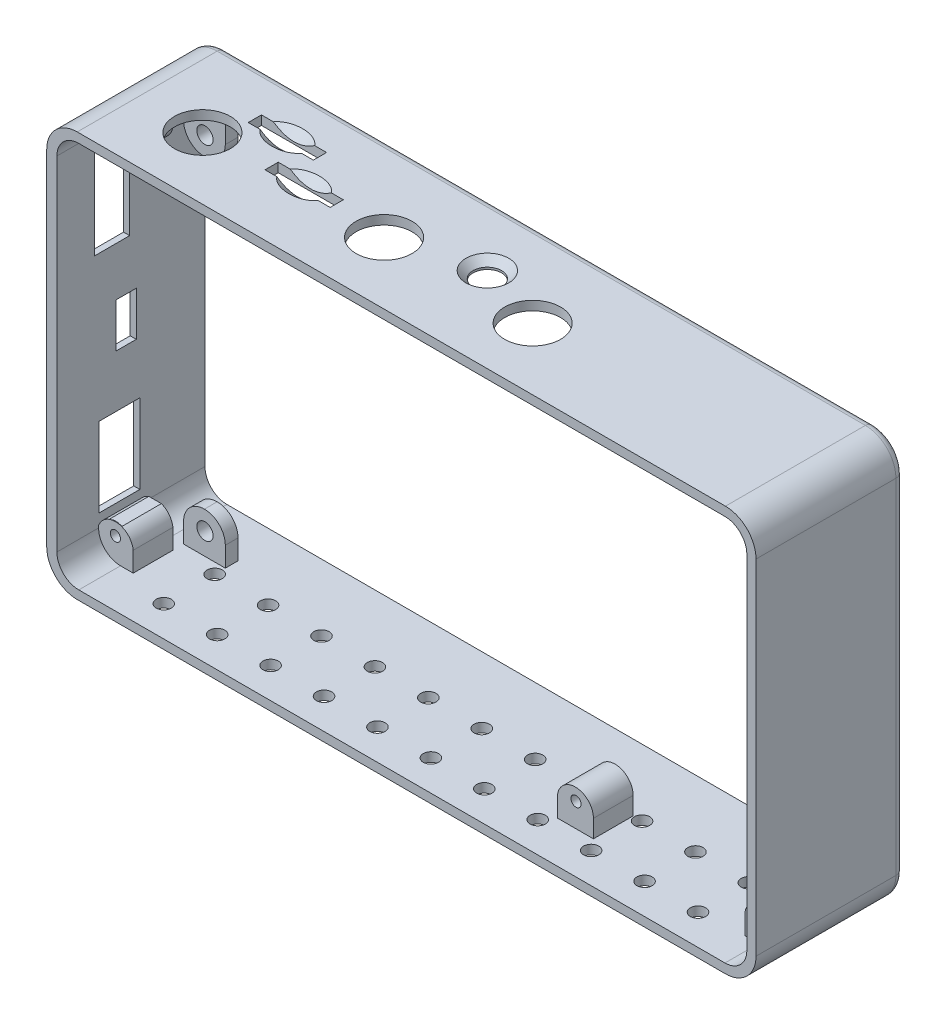
SolidWorks part; units mm, degrees
ref_plane "Спереди" through (0, 0, 0) normal (0, 0, 1) x (1, 0, 0)
ref_plane "Сверху" through (0, 0, 0) normal (0, 1, 0) x (1, 0, 0)
ref_plane "Справа" through (0, 0, 0) normal (1, 0, 0) x (0, 0, -1)
sketch "Эскиз1" plane through (0, 0, 0) normal (0, 0, 1) x (1, 0, 0)
  line L0 (-67.7, 32.8) -> (-67.7, -32.8)
  line L1 (-69.7, -33.9) -> (-69.7, 33.9)
  line L2 (-63.9, 38) -> (63.9, 38)
  line L3 (-64, 39.8) -> (64, 39.8)
  line L4 (-60.9, 34.5) -> (-60.9, 38)
  line L5 (-62.5165, 31.55) -> (-66.2835, 31.55)
  line L6 (-60.7, 33.8) -> (-60.7, 34.2)
  line L7 (29.55, 34.5) -> (29.55, 38)
  line L8 (22.45, 34.5) -> (22.45, 38)
  line L9 (56.9, 30) -> (56.5, 30)
  line L10 (60.7, 33.8) -> (60.7, 34.2)
  line L11 (60.9, 38) -> (60.9, 34.5)
  line L12 (67.9, -32.8) -> (67.9, 32.8)
  line L13 (69.7, 33.9) -> (69.7, -33.9)
  line L14 (60.9, -38) -> (60.9, -34.5)
  line L15 (67.9, -33) -> (67.9, -34)
  line L16 (59, -39.8) -> (62, -39.8)
  line L17 (59, -39.8) -> (-59, -39.8)
  line L18 (64, -39.8) -> (62, -39.8)
  line L19 (-63.9, -38) -> (63.9, -38)
  line L20 (22.45, -34.5) -> (22.45, -38)
  line L21 (29.55, -34.5) -> (29.55, -38)
  line L22 (-52.7, -33.8) -> (-52.7, -34.2)
  line L23 (-60.7, -33.8) -> (-60.7, -34.2)
  line L24 (-62, -39.8) -> (-64, -39.8)
  line L25 (-62, -39.8) -> (-59, -39.8)
  line L26 (-60.9, -34.5) -> (-60.9, -38)
  line L27 (-62.5165, -31.55) -> (-66.2835, -31.55)
  arc A0 (-63.9, 38) -> (-67.9, 34) centre (-63.9, 34) ccw
  circle A1 centre (-64.4, 34.5) radius 1
  arc A2 (-64, 39.8) -> (-69.7, 34.1) centre (-64, 34.1) ccw
  arc A3 (-62.5165, 31.55) -> (-60.9, 34.5) centre (-64.4, 34.5) ccw
  arc A4 (-66.2835, 31.55) -> (-62.5165, 31.55) centre (-64.4, 34.5) ccw
  arc A5 (-67.5623, 33) -> (-66.2835, 31.55) centre (-64.4, 34.5) ccw
  arc A6 (-60.7, 34.2) -> (-60.9, 35.4166) centre (-64.5, 34.2) ccw
  arc A7 (-60.7, 33.8) -> (-56.9, 30) centre (-56.9, 33.8) ccw
  arc A8 (-56.5, 30) -> (-52.7, 33.8) centre (-56.5, 33.8) ccw
  arc A9 (-48.9, 38) -> (-52.7, 34.2) centre (-48.9, 34.2) ccw
  circle A10 centre (-56.7, 33.7) radius 1.6
  arc A11 (22.45, 34.5) -> (29.55, 34.5) centre (26, 34.5) ccw
  circle A12 centre (26.1275, 34.6188) radius 1.5
  arc A13 (56.9, 30) -> (60.7, 33.8) centre (56.9, 33.8) ccw
  circle A14 centre (56.7, 33.7) radius 1.6
  arc A15 (52.7, 33.8) -> (56.5, 30) centre (56.5, 33.8) ccw
  arc A16 (52.7, 34.2) -> (48.9, 38) centre (48.9, 34.2) ccw
  arc A17 (60.9, 35.4166) -> (60.7, 34.2) centre (64.5, 34.2) ccw
  arc A18 (60.9, 34.5) -> (67.5623, 33) centre (64.4, 34.5) ccw
  circle A19 centre (64.4, 34.5) radius 1
  arc A20 (69.7, 34.1) -> (64, 39.8) centre (64, 34.1) ccw
  arc A21 (67.9, 34) -> (63.9, 38) centre (63.9, 34) ccw
  arc A22 (48.9, -38) -> (52.7, -34.2) centre (48.9, -34.2) ccw
  arc A23 (56.5, -30) -> (52.7, -33.8) centre (56.5, -33.8) ccw
  arc A24 (60.7, -33.8) -> (56.9, -30) centre (56.9, -33.8) ccw
  circle A25 centre (56.7, -33.7) radius 1.6
  arc A26 (67.5623, -33) -> (60.9, -34.5) centre (64.4, -34.5) ccw
  arc A27 (63.9, -38) -> (67.9, -34) centre (63.9, -34) ccw
  arc A28 (64, -39.8) -> (69.7, -34.1) centre (64, -34.1) ccw
  circle A29 centre (64.4, -34.5) radius 1
  circle A30 centre (26.1275, -33.3262) radius 1.5
  arc A31 (29.55, -34.5) -> (22.45, -34.5) centre (26, -34.5) ccw
  arc A32 (-52.7, -33.8) -> (-56.5, -30) centre (-56.5, -33.8) ccw
  arc A33 (-52.7, -34.2) -> (-48.9, -38) centre (-48.9, -34.2) ccw
  arc A34 (-56.9, -30) -> (-60.7, -33.8) centre (-56.9, -33.8) ccw
  circle A35 centre (-56.7, -33.7) radius 1.6
  arc A36 (-60.9, -35.4166) -> (-60.7, -34.2) centre (-64.5, -34.2) ccw
  arc A37 (-67.9, -34) -> (-63.9, -38) centre (-63.9, -34) ccw
  arc A38 (-69.7, -34.1) -> (-64, -39.8) centre (-64, -34.1) ccw
  arc A39 (-60.9, -34.5) -> (-62.5165, -31.55) centre (-64.4, -34.5) ccw
  arc A40 (-66.2835, -31.55) -> (-67.5623, -33) centre (-64.4, -34.5) ccw
  arc A41 (-62.5165, -31.55) -> (-66.2835, -31.55) centre (-64.4, -34.5) ccw
  circle A42 centre (-64.4, -33.4) radius 1
sketch "Эскиз2" plane through (0, 0, 0) normal (0, 0, 1) x (1, 0, 0)
  line L0 (-69.7, -33.9) -> (-69.7, 33.9) construction
  line L1 (-69.7, -39.8) -> (-69.7, 39.8)
  line L2 (-67.7, 32.8) -> (-67.7, -32.8) construction
  line L3 (-67.7, 38) -> (-67.7, -38)
  line L4 (-64, 39.8) -> (64, 39.8) construction
  line L5 (-69.7, 39.8) -> (69.7, 39.8)
  line L6 (-63.9, 38) -> (63.9, 38) construction
  line L7 (-67.7, 38) -> (67.9, 38)
  line L9 (69.7, 33.9) -> (69.7, -33.9) construction
  line L10 (69.7, 39.8) -> (69.7, -39.8)
  line L11 (67.9, -32.8) -> (67.9, 32.8) construction
  line L12 (67.9, -38) -> (67.9, 38)
  line L19 (-63.9, -38) -> (63.9, -38) construction
  line L20 (-67.7, -38) -> (67.9, -38)
  line L25 (59, -39.8) -> (-59, -39.8) construction
  line L26 (69.7, -39.8) -> (-69.7, -39.8)
  point P1 (-67.7, 37.7102)
  point P2 (69.7, 39.8)
  point P4 (-69.726, 39.8)
  point P5 (-69.7, 39.6686)
  point P8 (67.9, 38)
  point P9 (67.9, -38)
  point P12 (-67.7, 38)
  point P13 (67.7289, 38)
  point P15 (69.5498, 39.8)
  point P21 (67.7269, -38)
  point P22 (69.7, -39.8)
  point P24 (69.8908, -39.8)
  point P27 (-69.7, -39.8)
  point P28 (-67.7, -38)
  point P30 (-67.8826, -38)
  point P34 (-69.7, -39.5625)
  point P38 (0, 0)
  point P41 (0, 0)
  point P42 (0, 0)
  point P43 (0, 0)
  point P44 (-67.7, 37.9527)
other "Перо1"
extrude "Бобышка-Вытянуть1" add sketch "Эскиз2" along normal blind 29.1
fillet "Скругление2" radius 4.3 4 edges at (-67.7, 38, 14.55) (67.9, 38, 14.55) (67.9, -38, 14.55) (-67.7, -38, 14.55)
fillet "Скругление3" radius 6 4 edges at (-69.7, 39.8, 14.55) (69.7, 39.8, 14.55) (69.7, -39.8, 14.55) (-69.7, -39.8, 14.55)
fillet "Скругление4" radius 1.6 8 edges at (67.9426, 38.0426, 0) (69.7, 0, 0) (67.9426, -38.0426, 0) (0, -39.8, 0) (-67.9426, -38.0426, 0) (-69.7, 0, 0) (-67.9426, 38.0426, 0) (0, 39.8, 0)
sketch "Эскиз4" plane through (0, 0, 0) normal (0, 0, -1) x (-1, 0, 0)
  line L1 (-60.9, 38) -> (-52.7, 38)
  line L2 (-60.9, 38) -> (-60.9, 30)
  line L3 (-60.9, 30) -> (-52.7, 30)
  line L4 (-52.7, 38) -> (-52.7, 30)
  line L5 (60.9, 38) -> (52.7, 38)
  line L6 (60.9, 38) -> (60.9, 30)
  line L7 (60.9, 30) -> (52.7, 30)
  line L8 (52.7, 38) -> (52.7, 30)
  line L9 (60.9, -38) -> (52.7, -38)
  line L10 (60.9, -38) -> (60.9, -30)
  line L11 (60.9, -30) -> (52.7, -30)
  line L12 (52.7, -38) -> (52.7, -30)
  line L13 (-60.9, -38) -> (-52.7, -38)
  line L14 (-60.9, -38) -> (-60.9, -30)
  line L15 (-60.9, -30) -> (-52.7, -30)
  line L16 (-52.7, -38) -> (-52.7, -30)
extrude "Бобышка-Вытянуть2" add sketch "Эскиз4" against normal blind 11
sketch "Эскиз7" plane through (-52.7, 0, 0) normal (1, 0, 0) x (0, 0, -1)
  line L0 (-11, -38) -> (0, -38) construction
  line L1 (0, -30) -> (-8.5, -30)
  line L2 (0, -30) -> (0, -38)
  line L3 (0, -38) -> (-8.5, -38)
  line L4 (-8.5, -30) -> (-8.5, -38)
  dimension "D1" = 8.5
extrude "Вырез-Вытянуть1" cut sketch "Эскиз7" against normal blind 8.2
sketch "Эскиз8" plane through (-52.7, 0, 0) normal (1, 0, 0) x (0, 0, -1)
  line L0 (-11, 38) -> (0, 38) construction
  line L1 (0, 30) -> (-8.5, 30)
  line L2 (0, 30) -> (0, 38)
  line L3 (0, 38) -> (-8.5, 38)
  line L4 (-8.5, 30) -> (-8.5, 38)
  dimension "D1" = 8.5
extrude "Вырез-Вытянуть2" cut sketch "Эскиз8" against normal blind 8.2
sketch "Эскиз9" plane through (52.7, 0, 0) normal (-1, 0, 0) x (0, 0, 1)
  line L0 (11, 38) -> (0, 38) construction
  line L1 (0, 30) -> (8.5, 30)
  line L2 (0, 30) -> (0, 38)
  line L3 (0, 38) -> (8.5, 38)
  line L4 (8.5, 30) -> (8.5, 38)
  dimension "D1" = 8.5
extrude "Вырез-Вытянуть3" cut sketch "Эскиз9" against normal blind 8.2
sketch "Эскиз10" plane through (52.7, 0, 0) normal (-1, 0, 0) x (0, 0, 1)
  line L0 (11, -38) -> (0, -38) construction
  line L1 (0, -30) -> (8.5, -30)
  line L2 (0, -30) -> (0, -38)
  line L3 (0, -38) -> (8.5, -38)
  line L4 (8.5, -30) -> (8.5, -38)
  dimension "D1" = 8.5
extrude "Вырез-Вытянуть4" cut sketch "Эскиз10" against normal blind 8.2
sketch "Эскиз11" plane through (0, 0, 11) normal (0, 0, 1) x (1, 0, 0)
  circle A0 centre (-56.7, 33.7) radius 1.6 construction
  circle A1 centre (-56.7, 33.7) radius 1.6
  circle A2 centre (56.7, 33.7) radius 1.6 construction
  circle A3 centre (56.7, 33.7) radius 1.6
  circle A4 centre (56.7, -33.7) radius 1.6 construction
  circle A5 centre (56.7, -33.7) radius 1.6
  circle A6 centre (-56.7, -33.7) radius 1.6 construction
  circle A7 centre (-56.7, -33.7) radius 1.6
extrude "Вырез-Вытянуть5" cut sketch "Эскиз11" against normal blind 3
fillet "Скругление5" radius 4.1 8 edges at (60.9, -30, 9.75) (52.7, -30, 9.75) (52.7, 30, 9.75) (60.9, 30, 9.75) (-52.7, 30, 9.75) (-60.9, 30, 9.75) (-60.9, -30, 9.75) (-52.7, -30, 9.75)
sketch "Эскиз12" plane through (0, 0, 29.1) normal (0, 0, 1) x (1, 0, 0)
  line L0 (67.9, -33.7) -> (67.9, 33.7) construction
  line L1 (-67.7, 33.7) -> (-67.7, -33.7) construction
  line L2 (60.9, -38) -> (60.9, -34.5) construction
  line L3 (60.9, -38) -> (60.9, -34.5)
  line L4 (-63.4, -38) -> (63.6, -38) construction
  line L5 (-63.4, -38) -> (63.6, -38)
  line L6 (29.55, -34.5) -> (29.55, -38) construction
  line L7 (29.55, -34.5) -> (29.55, -38)
  line L8 (22.45, -34.5) -> (22.45, -38) construction
  line L9 (22.45, -34.5) -> (22.45, -38)
  line L10 (-60.9, -34.5) -> (-60.9, -38) construction
  line L11 (-60.9, -34.5) -> (-60.9, -38)
  line L12 (-67.7, 33.7) -> (-67.7, -33.7)
  line L13 (67.9, -33.7) -> (67.9, 33.7)
  line L14 (60.9, 38) -> (60.9, 34.5) construction
  line L15 (60.9, 38) -> (60.9, 34.5)
  line L16 (63.6, 38) -> (-63.4, 38) construction
  line L17 (63.6, 38) -> (-63.4, 38)
  line L18 (29.55, 34.5) -> (29.55, 38) construction
  line L19 (29.55, 34.5) -> (29.55, 38)
  line L20 (22.45, 34.5) -> (22.45, 38) construction
  line L21 (22.45, 34.5) -> (22.45, 38)
  line L22 (-60.9, 34.5) -> (-60.9, 38) construction
  line L23 (-60.9, 34.5) -> (-60.9, 38)
  line L24 (-60.9, -34.1) -> (-60.9, -34.5)
  arc A0 (60.9, 35.4166) -> (67.9, 33.5834) centre (64.4, 34.5) ccw
  arc A1 (22.45, 34.5) -> (29.55, 34.5) centre (26, 34.5) ccw
  arc A3 (-60.9, 34.5) -> (-67.7, 33.3338) centre (-64.4, 34.5) cw
  arc A4 (-60.9, -34.1) -> (-67.7, -33.2671) centre (-64.4, -34.5) ccw
  arc A5 (22.45, -34.5) -> (29.55, -34.5) centre (26, -34.5) cw
  arc A7 (60.9, -34.5) -> (67.8916, -34.2584) centre (64.4, -34.5) cw
  arc A8 (63.9, -38) -> (67.9, -34) centre (63.9, -34) ccw construction
  arc A10 (63.6, -38) -> (67.9, -33.7) centre (63.6, -33.7) ccw construction
  arc A11 (63.6, -38) -> (67.9, -33.7) centre (63.6, -33.7) ccw
  arc A12 (-67.7, -33.7) -> (-63.4, -38) centre (-63.4, -33.7) ccw construction
  arc A13 (-67.7, -33.7) -> (-63.4, -38) centre (-63.4, -33.7) ccw
  arc A14 (67.9, 33.7) -> (63.6, 38) centre (63.6, 33.7) ccw construction
  arc A15 (67.9, 33.7) -> (63.6, 38) centre (63.6, 33.7) ccw
  arc A16 (-63.4, 38) -> (-67.7, 33.7) centre (-63.4, 33.7) ccw construction
  arc A17 (-63.4, 38) -> (-67.7, 33.7) centre (-63.4, 33.7) ccw
extrude "Бобышка-Вытянуть3" add sketch "Эскиз12" against normal blind 16 separate body
sketch "Эскиз13" plane through (0, 0, 29.1) normal (0, 0, 1) x (1, 0, 0)
  line L2 (60.9, -34.5) -> (60.9, -38)
  line L3 (22.45, 38) -> (22.45, 34.5)
  line L4 (29.55, 34.5) -> (29.55, 38)
  line L5 (29.55, 38) -> (22.45, 38)
  line L6 (22.45, 38) -> (22.45, 34.5)
  line L7 (29.55, 34.5) -> (29.55, 38)
  line L8 (29.55, 38) -> (22.45, 38)
  line L9 (-60.9, 34.5) -> (-60.9, 38)
  line L10 (-60.9, 38) -> (-63.4, 38)
  line L11 (-67.7, 33.7) -> (-67.7, 33.3338)
  line L12 (-60.9, 34.5) -> (-60.9, 38)
  line L13 (-60.9, 38) -> (-63.4, 38)
  line L14 (-67.7, 33.7) -> (-67.7, 33.3338)
  line L15 (60.9, 38) -> (60.9, 35.4166)
  line L16 (67.9, 33.5834) -> (67.9, 33.7)
  line L17 (63.6, 38) -> (60.9, 38)
  line L18 (60.9, 38) -> (60.9, 35.4166)
  line L19 (67.9, 33.5834) -> (67.9, 33.7)
  line L20 (63.6, 38) -> (60.9, 38)
  line L21 (22.45, -34.5) -> (22.45, -38)
  line L22 (22.45, -38) -> (29.55, -38)
  line L23 (29.55, -38) -> (29.55, -34.5)
  line L24 (22.45, -34.5) -> (22.45, -38)
  line L25 (22.45, -38) -> (29.55, -38)
  line L26 (29.55, -38) -> (29.55, -34.5)
  line L27 (60.9, -38) -> (63.6, -38)
  line L28 (60.9, -34.5) -> (60.9, -38)
  line L29 (60.9, -38) -> (63.6, -38)
  line L31 (-60.9, -38) -> (-60.9, -34.1)
  line L32 (-67.7, -33.2671) -> (-67.7, -33.7)
  line L33 (-63.4, -38) -> (-60.9, -38)
  line L34 (-60.9, -38) -> (-60.9, -34.1)
  line L35 (-67.7, -33.2671) -> (-67.7, -33.7)
  line L36 (-63.4, -38) -> (-60.9, -38)
  arc A1 (22.45, 34.5) -> (29.55, 34.5) centre (26, 34.5) ccw
  arc A2 (22.45, 34.5) -> (29.55, 34.5) centre (26, 34.5) ccw
  arc A3 (29.55, -34.5) -> (22.45, -34.5) centre (26, -34.5) ccw
  arc A4 (-67.7, 33.3338) -> (-60.9, 34.5) centre (-64.4, 34.5) ccw
  arc A5 (-63.4, 38) -> (-67.7, 33.7) centre (-63.4, 33.7) ccw
  arc A6 (-67.7, 33.3338) -> (-60.9, 34.5) centre (-64.4, 34.5) ccw
  arc A7 (-63.4, 38) -> (-67.7, 33.7) centre (-63.4, 33.7) ccw
  arc A8 (60.9, 35.4166) -> (67.9, 33.5834) centre (64.4, 34.5) ccw
  arc A9 (67.9, 33.7) -> (63.6, 38) centre (63.6, 33.7) ccw
  arc A10 (60.9, 35.4166) -> (67.9, 33.5834) centre (64.4, 34.5) ccw
  arc A11 (67.9, 33.7) -> (63.6, 38) centre (63.6, 33.7) ccw
  arc A12 (29.55, -34.5) -> (22.45, -34.5) centre (26, -34.5) ccw
  arc A14 (67.8794, -34.1206) -> (60.9, -34.5) centre (64.4, -34.5) ccw
  arc A15 (63.6, -38) -> (67.8794, -34.1206) centre (63.6, -33.7) ccw
  arc A16 (67.8794, -34.1206) -> (60.9, -34.5) centre (64.4, -34.5) ccw
  arc A17 (63.6, -38) -> (67.8794, -34.1206) centre (63.6, -33.7) ccw
  arc A18 (-60.9, -34.1) -> (-67.7, -33.2671) centre (-64.4, -34.5) ccw
  arc A19 (-67.7, -33.7) -> (-63.4, -38) centre (-63.4, -33.7) ccw
  arc A20 (-60.9, -34.1) -> (-67.7, -33.2671) centre (-64.4, -34.5) ccw
  arc A21 (-67.7, -33.7) -> (-63.4, -38) centre (-63.4, -33.7) ccw
  dimension "D1" = 0
  dimension "D2" = 0
  dimension "D3" = 0
  dimension "D4" = 0
  dimension "D5" = 0
  dimension "D6" = 0
extrude "Вырез-Вытянуть6" cut sketch "Эскиз13" against normal blind 8.2
sketch "Эскиз14" plane through (0, 0, 20.9) normal (0, 0, 1) x (1, 0, 0)
  circle A0 centre (-64.4, 34.5) radius 1 construction
  circle A1 centre (-64.4, 34.5) radius 1
  circle A2 centre (-64.4, -33.4) radius 1 construction
  circle A3 centre (-64.4, -33.4) radius 1
  circle A4 centre (64.4, -34.5) radius 1 construction
  circle A5 centre (64.4, -34.5) radius 1
  circle A6 centre (64.4, 34.5) radius 1 construction
  circle A7 centre (64.4, 34.5) radius 1
  circle A8 centre (26.1275, 34.6188) radius 1
  circle A9 centre (26.1275, -33.3262) radius 1
  dimension "D1" = 2
  dimension "D2" = 2
extrude "Вырез-Вытянуть7" cut sketch "Эскиз14" against normal blind 8
sketch "Эскиз15" plane through (0, 0, 20.9) normal (0, 0, 1) x (1, 0, 0)
  line L2 (60.9, -34.5) -> (60.9, -38)
  line L3 (63.6, 38) -> (60.9, 38)
  line L4 (60.9, 38) -> (60.9, 35.4166)
  line L5 (67.9, 33.5834) -> (67.9, 33.7)
  line L6 (63.6, 38) -> (60.9, 38)
  line L7 (60.9, 38) -> (60.9, 35.4166)
  line L8 (67.9, 33.5834) -> (67.9, 33.7)
  line L9 (60.9, -38) -> (63.6, -38)
  line L10 (60.9, -34.5) -> (60.9, -38)
  line L11 (60.9, -38) -> (63.6, -38)
  circle A0 centre (64.4, 34.5) radius 1 construction
  circle A1 centre (64.4, 34.5) radius 1
  arc A2 (60.9, 35.4166) -> (67.9, 33.5834) centre (64.4, 34.5) ccw
  arc A3 (67.9, 33.7) -> (63.6, 38) centre (63.6, 33.7) ccw
  arc A4 (60.9, 35.4166) -> (67.9, 33.5834) centre (64.4, 34.5) ccw
  arc A5 (67.9, 33.7) -> (63.6, 38) centre (63.6, 33.7) ccw
  circle A6 centre (64.4, -34.5) radius 1 construction
  circle A7 centre (64.4, -34.5) radius 1
  arc A8 (63.6, -38) -> (67.8794, -34.1206) centre (63.6, -33.7) ccw
  arc A9 (67.8794, -34.1206) -> (60.9, -34.5) centre (64.4, -34.5) ccw
  arc A10 (63.6, -38) -> (67.8794, -34.1206) centre (63.6, -33.7) ccw
  arc A11 (67.8794, -34.1206) -> (60.9, -34.5) centre (64.4, -34.5) ccw
  dimension "D1" = 0
  dimension "D2" = 0
extrude "Бобышка-Вытянуть4" add sketch "Эскиз15" along normal blind 1.6
sketch "Эскиз16" plane through (0, 39.8, 0) normal (0, 1, 0) x (1, 0, 0)
  line L0 (63.7, -29.1) -> (-63.7, -29.1) construction
  line L1 (-48.5, -8.1) -> (-35.7, -8.1)
  line L2 (-48.5, -8.1) -> (-48.5, -10.7)
  line L3 (-48.5, -10.7) -> (-35.7, -10.7)
  line L4 (-35.7, -8.1) -> (-35.7, -10.7)
  line L5 (-38.8, -14.5) -> (-26, -14.5)
  line L6 (-38.8, -14.5) -> (-38.8, -17.1)
  line L7 (-38.8, -17.1) -> (-26, -17.1)
  line L8 (-26, -14.5) -> (-26, -17.1)
  line L9 (-69.7, -29.1) -> (-69.7, -1.6) construction
  line L10 (-63.7, 0) -> (63.7, 0) construction
  circle A0 centre (-51.3, -16.9) radius 5.5
  circle A1 centre (-15.6, -16.9) radius 5.5
  circle A2 centre (0.2, -12.4) radius 2.8
  circle A3 centre (13.6, -16.9) radius 5.5
  dimension "D1" = 11
  dimension "D2" = 12.2
  dimension "D3" = 18.4
  dimension "D4" = 12.2
  dimension "D5" = 12.2
  dimension "D6" = 5.6
  dimension "D7" = 16.7
  dimension "D8" = 35.7
  dimension "D9" = 69.9
  dimension "D10" = 29.2
  dimension "D11" = 12.8
  dimension "D12" = 12.8
  dimension "D13" = 2.6
  dimension "D14" = 2.6
  dimension "D15" = 8.1
  dimension "D16" = 12
  dimension "D17" = 21.2
  dimension "D18" = 30.9
extrude "Вырез-Вытянуть9" cut sketch "Эскиз16" against normal blind 2
sketch "Эскиз17" plane through (0, 39.8, 0) normal (0, 1, 0) x (1, 0, 0)
  line L1 (-42.1, -4.2544) -> (-42.1, -15.8144) construction
  line L2 (-51.0323, -9.4) -> (-33.3327, -9.4) construction
  line L3 (-39.9974, -15.8) -> (-24.7378, -15.8) construction
  line L4 (-32.4, -10.6642) -> (-32.4, -20.4245) construction
  line L5 (-35.7, -8.1) -> (-48.5, -8.1) construction
  line L6 (-26, -14.5) -> (-38.8, -14.5) construction
  line L7 (-35.7, -10.7) -> (-35.7, -8.1) construction
  line L8 (-26, -17.1) -> (-26, -14.5) construction
  ellipse E0 centre (-42.1, -9.4046) end of major axis (-37.6, -9.4046) minor radius 3
  ellipse E1 centre (-32.4, -15.8144) end of major axis (-27.9, -15.8144) minor radius 3
  point P28 (0, 0)
  point P29 (0, 0)
  dimension "D1" = 9
  dimension "D2" = 9
  dimension "D3" = 6
  dimension "D4" = 6
  dimension "D5" = 1.3
  dimension "D6" = 1.3
  dimension "D7" = 6.4
  dimension "D8" = 6.4
extrude "Вырез-Вытянуть10" cut sketch "Эскиз17" against normal blind 1.6 draft 51
chamfer "Фаска1" distance 1.4 angle 45 1 edges at (-2.6, 39.8, 12.4)
sketch "Эскиз20" plane through (0, 38, 0) normal (0, -1, 0) x (1, 0, 0)
  line L1 (-43.9, 20.9) -> (-42.7, 20.9)
  line L2 (-43.9, 20.9) -> (-43.9, 12.9)
  line L3 (-43.9, 12.9) -> (-42.7, 12.9)
  line L4 (-42.7, 20.9) -> (-42.7, 12.9)
  line L5 (-8.6, 20.9) -> (-7.4, 20.9)
  line L6 (-8.6, 20.9) -> (-8.6, 12.9)
  line L7 (-8.6, 12.9) -> (-7.4, 12.9)
  line L8 (-7.4, 20.9) -> (-7.4, 12.9)
  line L9 (20.2, 20.9) -> (21.4, 20.9)
  line L10 (20.2, 20.9) -> (20.2, 12.9)
  line L11 (20.2, 12.9) -> (21.4, 12.9)
  line L12 (21.4, 20.9) -> (21.4, 12.9)
  circle A0 centre (13.6, 16.9) radius 5.5 construction
  circle A1 centre (-15.6, 16.9) radius 5.5 construction
  circle A2 centre (-51.3, 16.9) radius 5.5 construction
  dimension "D1" = 1.2
  dimension "D2" = 1.2
  dimension "D3" = 1.2
  dimension "D4" = 6.6
  dimension "D5" = 7
  dimension "D6" = 7.4
  dimension "D7" = 4
  dimension "D8" = 4
extrude "Бобышка-Вытянуть5" add sketch "Эскиз20" along normal blind 1.6
sketch "Эскиз21" plane through (-69.7, 0, 0) normal (-1, 0, 0) x (0, 0, 1)
  line L0 (1.6, 39.8) -> (29.1, 39.8) construction
  line L1 (14.8, 31.6) -> (21.7, 31.6)
  line L2 (14.8, 31.6) -> (14.8, 13)
  line L3 (14.8, 13) -> (21.7, 13)
  line L4 (21.7, 31.6) -> (21.7, 13)
  line L5 (13.5, 3.4) -> (17.5, 3.4)
  line L6 (13.5, 3.4) -> (13.5, -5.3)
  line L7 (13.5, -5.3) -> (17.5, -5.3)
  line L8 (17.5, 3.4) -> (17.5, -5.3)
  line L9 (12.8, -15.6) -> (20.8, -15.6)
  line L10 (12.8, -15.6) -> (12.8, -31.2)
  line L11 (12.8, -31.2) -> (20.8, -31.2)
  line L12 (20.8, -15.6) -> (20.8, -31.2)
  line L13 (29.1, 33.8) -> (29.1, -33.8) construction
  line L14 (29.1, -39.8) -> (1.6, -39.8) construction
  dimension "D1" = 8.2
  dimension "D2" = 7.4
  dimension "D3" = 6.9
  dimension "D4" = 18.6
  dimension "D5" = 36.4
  dimension "D6" = 11.6
  dimension "D7" = 8.7
  dimension "D8" = 4
  dimension "D9" = 8
  dimension "D10" = 15.6
  dimension "D11" = 8.3
  dimension "D12" = 8.6
extrude "Вырез-Вытянуть12" cut sketch "Эскиз21" against normal blind 12
sketch "Эскиз22" plane through (-69.7, 0, 0) normal (-1, 0, 0) x (0, 0, 1)
  line L0 (21.7, 31.6) -> (14.8, 31.6) construction
  line L1 (13.8, 32.6) -> (22.7, 32.6)
  line L2 (13.8, 32.6) -> (13.8, 12)
  line L3 (13.8, 12) -> (22.7, 12)
  line L4 (22.7, 32.6) -> (22.7, 12)
  line L5 (12.5, 4.4) -> (18.5, 4.4)
  line L6 (12.5, 4.4) -> (12.5, -6.3)
  line L7 (12.5, -6.3) -> (18.5, -6.3)
  line L8 (18.5, 4.4) -> (18.5, -6.3)
  line L9 (11.8, -14.6) -> (21.8, -14.6)
  line L10 (11.8, -14.6) -> (11.8, -32.2)
  line L11 (11.8, -32.2) -> (21.8, -32.2)
  line L12 (21.8, -14.6) -> (21.8, -32.2)
  line L13 (14.8, 31.6) -> (14.8, 13) construction
  line L14 (14.8, 13) -> (21.7, 13) construction
  line L15 (21.7, 13) -> (21.7, 31.6) construction
  line L16 (17.5, 3.4) -> (13.5, 3.4) construction
  line L17 (13.5, -5.3) -> (17.5, -5.3) construction
  line L18 (17.5, -5.3) -> (17.5, 3.4) construction
  line L19 (13.5, 3.4) -> (13.5, -5.3) construction
  line L20 (20.8, -15.6) -> (12.8, -15.6) construction
  line L21 (12.8, -15.6) -> (12.8, -31.2) construction
  line L22 (20.8, -31.2) -> (20.8, -15.6) construction
  line L23 (12.8, -31.2) -> (20.8, -31.2) construction
  dimension "D1" = 1
  dimension "D2" = 1
  dimension "D3" = 1
  dimension "D4" = 1
  dimension "D5" = 1
  dimension "D6" = 1
  dimension "D7" = 1
  dimension "D8" = 1
  dimension "D9" = 1
  dimension "D10" = 1
  dimension "D11" = 1
  dimension "D12" = 1
extrude "Вырез-Вытянуть14" cut sketch "Эскиз22" against normal blind 0.8
fillet "Скругление6" radius 0.8 12 edges at (-69.7, 12, 18.25) (-69.7, 22.3, 22.7) (-69.7, 32.6, 18.25) (-69.7, 22.3, 13.8) (-69.7, -32.2, 16.8) (-69.7, -23.4, 11.8) (-69.7, -23.4, 21.8) (-69.7, -14.6, 16.8) (-69.7, -6.3, 15.5) (-69.7, -0.95, 12.5) (-69.7, 4.4, 15.5) (-69.7, -0.95, 18.5)
sketch "Эскиз23" plane through (0, -39.8, 0) normal (0, -1, 0) x (1, 0, 0)
  line L0 (-63.7, 29.1) -> (63.7, 29.1) construction
  line L1 (-60.7, 29.1) -> (-58.7, 29.1)
  line L2 (-60.7, 29.1) -> (-60.7, 2)
  line L3 (-60.7, 2) -> (-58.7, 2)
  line L4 (-58.7, 29.1) -> (-58.7, 2)
  line L5 (-63.7, 29.1) -> (-63.7, 1.6) construction
  line L6 (57.7, 29.1) -> (60.7, 29.1)
  line L7 (57.7, 29.1) -> (57.7, 2)
  line L8 (57.7, 2) -> (60.7, 2)
  line L9 (60.7, 29.1) -> (60.7, 2)
  line L11 (63.7, 0) -> (-63.7, 0) construction
  line L12 (63.7, 1.6) -> (63.7, 29.1) construction
  dimension "D1" = 3
  dimension "D2" = 2
  dimension "D3" = 2
  dimension "D4" = 2
  dimension "D5" = 3
  dimension "D6" = 3
extrude "Бобышка-Вытянуть6" add sketch "Эскиз23" along normal blind 2
chamfer "Фаска2" distance 2 angle 45 4 edges at (-59.7, -41.8, 29.1) (-59.7, -41.8, 2) (59.2, -41.8, 2) (59.2, -41.8, 29.1)
sketch "Эскиз24" plane through (0, -39.8, 0) normal (0, -1, 0) x (1, 0, 0)
  line L0 (-58.7, 29.1) -> (57.7, 29.1) construction
  line L1 (-58.7, 4) -> (-58.7, 27.1) construction
  circle A0 centre (-52.7, 23.1) radius 1.5
  circle A1 centre (-42.2, 23.1) radius 1.5
  circle A2 centre (-31.7, 23.1) radius 1.5
  circle A3 centre (-21.2, 23.1) radius 1.5
  circle A4 centre (-10.7, 23.1) radius 1.5
  circle A5 centre (-0.2, 23.1) radius 1.5
  circle A6 centre (10.3, 23.1) radius 1.5
  circle A7 centre (20.8, 23.1) radius 1.5
  circle A8 centre (31.3, 23.1) radius 1.5
  circle A9 centre (41.8, 23.1) radius 1.5
  circle A10 centre (52.3, 23.1) radius 1.5
  circle A11 centre (-42.2, 13.1) radius 1.5
  circle A12 centre (-31.7, 13.1) radius 1.5
  circle A13 centre (-21.2, 13.1) radius 1.5
  circle A14 centre (-10.7, 13.1) radius 1.5
  circle A15 centre (-0.2, 13.1) radius 1.5
  circle A16 centre (10.3, 13.1) radius 1.5
  circle A17 centre (20.8, 13.1) radius 1.5
  circle A18 centre (31.3, 13.1) radius 1.5
  circle A19 centre (41.8, 13.1) radius 1.5
  circle A20 centre (52.3, 13.1) radius 1.5
  circle A21 centre (-52.7, 13.1) radius 1.5
  dimension "D1" = 3
  dimension "D2" = 6
  dimension "D3" = 6
  dimension "D4" = 11
  dimension "D5" = 2
extrude "Вырез-Вытянуть15" cut sketch "Эскиз24" against normal blind 2
